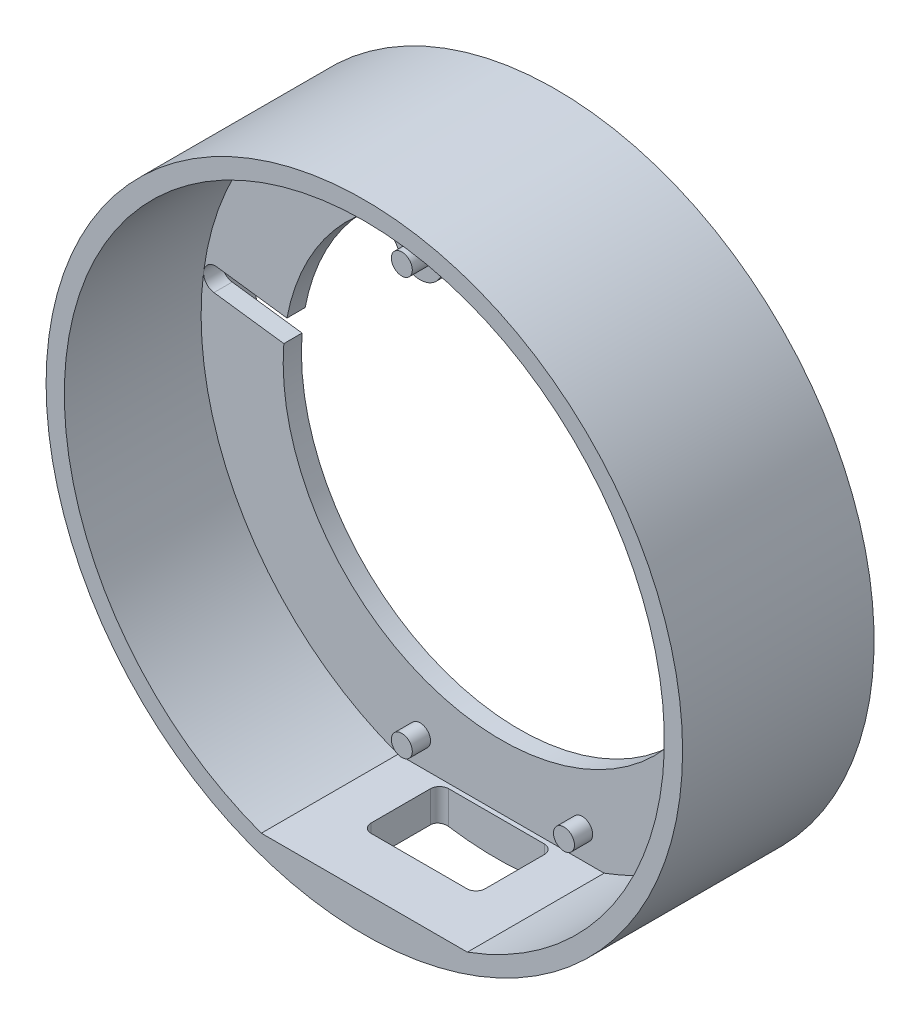
SolidWorks part; units mm, degrees
ref_plane "Plan de face" through (0, 0, 0) normal (0, 0, 1) x (1, 0, 0)
ref_plane "Plan de dessus" through (0, 0, 0) normal (0, 1, 0) x (1, 0, 0)
ref_plane "Plan de droite" through (0, 0, 0) normal (1, 0, 0) x (0, 0, -1)
sketch "Esquisse_carte_affichage" plane through (0, 0, 0) normal (0, 0, 1) x (1, 0, 0)
  circle A0 centre (19.25, 25.1) radius 0.5
  circle A1 centre (25.07, -19.23) radius 0.5
  circle A2 centre (29.18, 12.09) radius 0.5
  circle A3 centre (31.32, -4.14) radius 0.5
  circle A4 centre (-29.21, -12.07) radius 0.5
  circle A5 centre (-31.32, 4.14) radius 0.5
  circle A6 centre (-26.4935, -7.4094) radius 0.25
  circle A7 centre (-23.6728, -14.0139) radius 0.25
  circle A8 centre (-19.2392, -19.6637) radius 0.25
  circle A9 centre (-13.4943, -23.973) radius 0.25
  circle A10 centre (-6.8298, -26.6487) radius 0.25
  circle A11 centre (0.3, -27.5085) radius 0.25
  circle A12 centre (7.4094, -26.4935) radius 0.25
  circle A13 centre (14.0139, -23.6728) radius 0.25
  circle A14 centre (19.6637, -19.2392) radius 0.25
  circle A15 centre (23.973, -13.4943) radius 0.25
  circle A16 centre (26.6487, -6.8298) radius 0.25
  circle A17 centre (27.5085, 0.3) radius 0.25
  circle A18 centre (26.4935, 7.4094) radius 0.25
  circle A19 centre (23.6728, 14.0139) radius 0.25
  circle A20 centre (19.2392, 19.6637) radius 0.25
  circle A21 centre (13.4943, 23.973) radius 0.25
  circle A22 centre (6.8298, 26.6487) radius 0.25
  circle A23 centre (-0.3, 27.5085) radius 0.25
  circle A24 centre (-7.4094, 26.4935) radius 0.25
  circle A25 centre (-14.0139, 23.6728) radius 0.25
  circle A26 centre (-19.6637, 19.2392) radius 0.25
  circle A27 centre (-23.973, 13.4943) radius 0.25
  circle A28 centre (-26.6487, 6.8298) radius 0.25
  circle A29 centre (-27.5085, -0.3) radius 0.25
  circle A30 centre (-30.2, -7.1) radius 0.25
  circle A31 centre (-26.5986, -15.746) radius 0.25
  circle A32 centre (-28.1305, -7.8674) radius 0.25
  circle A33 centre (-21.6169, -22.0937) radius 0.25
  circle A34 centre (-25.1358, -14.8801) radius 0.25
  circle A35 centre (-15.162, -26.9359) radius 0.25
  circle A36 centre (-20.428, -20.8785) radius 0.25
  circle A37 centre (-7.6738, -29.9423) radius 0.25
  circle A38 centre (-14.3281, -25.4544) radius 0.25
  circle A39 centre (0.3371, -30.9082) radius 0.25
  circle A40 centre (-7.252, -28.2956) radius 0.25
  circle A41 centre (8.3254, -29.7678) radius 0.25
  circle A42 centre (0.3185, -29.2082) radius 0.25
  circle A43 centre (15.746, -26.5986) radius 0.25
  circle A44 centre (7.8674, -28.1305) radius 0.25
  circle A45 centre (22.0937, -21.6169) radius 0.25
  circle A46 centre (14.8801, -25.1358) radius 0.25
  circle A47 centre (26.9359, -15.162) radius 0.25
  circle A48 centre (20.8785, -20.428) radius 0.25
  circle A49 centre (29.9423, -7.6738) radius 0.25
  circle A50 centre (25.4544, -14.3281) radius 0.25
  circle A51 centre (30.9082, 0.3371) radius 0.25
  circle A52 centre (28.2956, -7.252) radius 0.25
  circle A53 centre (29.7678, 8.3254) radius 0.25
  circle A54 centre (29.2082, 0.3185) radius 0.25
  circle A55 centre (26.5986, 15.746) radius 0.25
  circle A56 centre (28.1305, 7.8674) radius 0.25
  circle A57 centre (21.6169, 22.0937) radius 0.25
  circle A58 centre (25.1358, 14.8801) radius 0.25
  circle A59 centre (15.162, 26.9359) radius 0.25
  circle A60 centre (20.428, 20.8785) radius 0.25
  circle A61 centre (7.6738, 29.9423) radius 0.25
  circle A62 centre (14.3281, 25.4544) radius 0.25
  circle A63 centre (-0.3371, 30.9082) radius 0.25
  circle A64 centre (7.252, 28.2956) radius 0.25
  circle A65 centre (-8.3254, 29.7678) radius 0.25
  circle A66 centre (-0.3185, 29.2082) radius 0.25
  circle A67 centre (-15.746, 26.5986) radius 0.25
  circle A68 centre (-7.8674, 28.1305) radius 0.25
  circle A69 centre (-22.0937, 21.6169) radius 0.25
  circle A70 centre (-14.8801, 25.1358) radius 0.25
  circle A71 centre (-26.9359, 15.162) radius 0.25
  circle A72 centre (-20.8785, 20.428) radius 0.25
  circle A73 centre (-29.9423, 7.6738) radius 0.25
  circle A74 centre (-25.4544, 14.3281) radius 0.25
  circle A75 centre (-30.9082, -0.3371) radius 0.25
  circle A76 centre (-28.2956, 7.252) radius 0.25
  circle A77 centre (0, 0) radius 26.162
  circle A78 centre (0, 0) radius 32.766
  dimension "D1" = 65.532
  dimension "D2" = 52.324
sketch "Esquisse_carte_mère" plane through (0, 0, 0) normal (0, 0, 1) x (1, 0, 0)
  line L0 (-11.3435, -28.5174) -> (-11.0897, -29.13)
  line L1 (-11.0897, -29.13) -> (-10.6861, -29.6561)
  line L2 (-10.6861, -29.6561) -> (-10.16, -30.0597)
  line L3 (-10.16, -30.0597) -> (-9.5474, -30.3135)
  line L4 (-9.5474, -30.3135) -> (-8.89, -30.4)
  line L5 (-8.89, -30.4) -> (-2.413, -30.4)
  line L6 (-2.413, -30.4) -> (-1.905, -29.892)
  line L7 (-1.905, -29.892) -> (1.905, -29.892)
  line L8 (1.905, -29.892) -> (2.413, -30.4)
  line L9 (2.413, -30.4) -> (8.89, -30.4)
  line L10 (8.89, -30.4) -> (9.5474, -30.3135)
  line L11 (9.5474, -30.3135) -> (10.16, -30.0597)
  line L12 (10.16, -30.0597) -> (10.6861, -29.6561)
  line L13 (10.6861, -29.6561) -> (11.0897, -29.13)
  line L14 (11.0897, -29.13) -> (11.3435, -28.5174)
  line L15 (11.3435, -28.5174) -> (11.43, -27.86)
  line L16 (11.43, -27.86) -> (11.43, 17.86)
  line L17 (11.43, 17.86) -> (11.3435, 18.5174)
  line L18 (11.3435, 18.5174) -> (11.0897, 19.13)
  line L19 (11.0897, 19.13) -> (10.6861, 19.6561)
  line L20 (10.6861, 19.6561) -> (10.16, 20.0597)
  line L21 (10.16, 20.0597) -> (9.5474, 20.3135)
  line L22 (9.5474, 20.3135) -> (8.89, 20.4)
  line L23 (8.89, 20.4) -> (-8.89, 20.4)
  line L24 (-8.89, 20.4) -> (-9.5474, 20.3135)
  line L25 (-9.5474, 20.3135) -> (-10.16, 20.0597)
  line L26 (-10.16, 20.0597) -> (-10.6861, 19.6561)
  line L27 (-10.6861, 19.6561) -> (-11.0897, 19.13)
  line L28 (-11.0897, 19.13) -> (-11.3435, 18.5174)
  line L29 (-11.3435, 18.5174) -> (-11.43, 17.86)
  line L30 (-11.43, 17.86) -> (-11.43, -27.86)
  line L31 (-11.43, -27.86) -> (-11.3435, -28.5174)
  line L32 (8.9522, -28.0199) -> (-18113.3609, 46572.2136) construction
  line L33 (-8.9266, -27.9541) -> (18113.3865, 46572.2795) construction
  circle A0 centre (-3.3, -25.05) radius 0.4
  circle A1 centre (3.3, -25.05) radius 0.4
  circle A2 centre (-3.6, -27.86) radius 0.45
  circle A3 centre (3.6, -27.86) radius 0.45
  circle A4 centre (10.16, 14.05) radius 0.5
  circle A5 centre (10.16, 11.51) radius 0.5
  circle A6 centre (10.16, 8.97) radius 0.5
  circle A7 centre (10.16, 6.43) radius 0.5
  circle A8 centre (10.16, 3.89) radius 0.5
  circle A9 centre (10.16, 1.35) radius 0.5
  circle A10 centre (10.16, -1.19) radius 0.5
  circle A11 centre (10.16, -3.73) radius 0.5
  circle A12 centre (10.16, -6.27) radius 0.5
  circle A13 centre (10.16, -8.81) radius 0.5
  circle A14 centre (10.16, -11.35) radius 0.5
  circle A15 centre (10.16, -13.89) radius 0.5
  circle A16 centre (-10.16, -24.05) radius 0.5
  circle A17 centre (-10.16, -21.51) radius 0.5
  circle A18 centre (-10.16, -18.97) radius 0.5
  circle A19 centre (-10.16, -16.43) radius 0.5
  circle A20 centre (-10.16, -13.89) radius 0.5
  circle A21 centre (-10.16, -11.35) radius 0.5
  circle A22 centre (-10.16, -8.81) radius 0.5
  circle A23 centre (-10.16, -6.27) radius 0.5
  circle A24 centre (-10.16, -3.73) radius 0.5
  circle A25 centre (-10.16, -1.19) radius 0.5
  circle A26 centre (-10.16, 1.35) radius 0.5
  circle A27 centre (-10.16, 3.89) radius 0.5
  circle A28 centre (-10.16, 6.43) radius 0.5
  circle A29 centre (-10.16, 8.97) radius 0.5
  circle A30 centre (-10.16, 11.51) radius 0.5
  circle A31 centre (-10.16, 14.05) radius 0.5
  circle A32 centre (-8.89, -27.86) radius 1.25
  circle A33 centre (8.89, -27.86) radius 1.25
  circle A34 centre (-8.89, 17.86) radius 1.25
  circle A35 centre (8.89, 17.86) radius 1.25
  circle A36 centre (-1.95, -25.955) radius 0.35
  circle A37 centre (1.95, -25.955) radius 0.35
  circle A38 centre (-2.2, 15.706) radius 0.45
  circle A39 centre (3.048, -15.795) radius 0.25
  circle A40 centre (1.016, -20.875) radius 0.25
  circle A41 centre (-6.223, -9.826) radius 0.25
  circle A42 centre (-6.096, -16.43) radius 0.25
  circle A43 centre (7.3914, -2.0028) radius 0.25
  circle A44 centre (7.366, -18.462) radius 0.25
  circle A45 centre (-1.905, 12.018) radius 0.25
  circle A46 centre (1.905, 9.224) radius 0.25
  circle A47 centre (-5.715, -21.129) radius 0.25
  circle A48 centre (-4.064, -1.571) radius 0.25
  circle A49 centre (-8.509, -22.78) radius 0.25
  circle A50 centre (0.2286, -14.5758) radius 0.25
  circle A51 centre (0.508, 7.446) radius 0.25
  circle A52 centre (0.635, 8.589) radius 0.25
  circle A53 centre (-7.112, 0.334) radius 0.25
  circle A54 centre (4.953, -15.795) radius 0.25
  circle A55 centre (0, 10.494) radius 0.25
  circle A56 centre (-4.191, -16.43) radius 0.25
  circle A57 centre (-0.889, -17.573) radius 0.25
  circle A58 centre (5.842, -10.715) radius 0.25
  circle A59 centre (2.159, -17.446) radius 0.25
  circle A60 centre (0, -27.987) radius 0.25
  circle A61 centre (-1.397, 4.271) radius 0.25
  circle A62 centre (-5.207, 1.985) radius 0.25
  circle A63 centre (-0.381, -6.651) radius 0.25
  circle A64 centre (6.858, 8.462) radius 0.25
  circle A65 centre (5.207, 3.128) radius 0.25
  circle A66 centre (2.667, 4.525) radius 0.25
  circle A67 centre (5.08, 11.764) radius 0.25
  circle A68 centre (0, 14.431) radius 0.25
  circle A69 centre (-1.778, 8.716) radius 0.25
  circle A70 centre (-2.921, 4.271) radius 0.25
  circle A71 centre (-5.588, 3.128) radius 0.25
  circle A72 centre (-1.905, -19.732) radius 0.25
  circle A73 centre (-5.842, -8.683) radius 0.25
  circle A74 centre (-3.048, -20.113) radius 0.25
  circle A75 centre (-6.604, -7.667) radius 0.25
  circle A76 centre (-5.207, -10.842) radius 0.25
  circle A77 centre (10.668, -26.082) radius 0.25
  circle A78 centre (5.969, -4.365) radius 0.25
  circle A79 centre (5.08, -9.191) radius 0.25
  circle A80 centre (-3.81, -3.349) radius 0.25
  circle A81 centre (-4.953, -9.699) radius 0.25
  circle A82 centre (3.048, 6.43) radius 0.25
  circle A83 centre (5.969, -3.222) radius 0.25
  circle A84 centre (6.858, -7.667) radius 0.25
  circle A85 centre (6.477, 6.303) radius 0.25
  circle A86 centre (-1.27, 10.367) radius 0.25
  circle A87 centre (-1.0922, -0.1994) radius 0.25
  circle A88 centre (0.508, -0.428) radius 0.25
  circle A89 centre (4.318, -17.065) radius 0.25
  circle A90 centre (1.524, 4.144) radius 0.25
  circle A91 centre (-2.921, -1.444) radius 0.25
  circle A92 centre (3.302, -10.08) radius 0.25
  circle A93 centre (-3.81, -10.08) radius 0.25
  circle A94 centre (-5.08, -6.778) radius 0.25
  point P222 (0, -5)
  dimension "D5" = 2.5
  dimension "D1" = 2.54
  dimension "D2" = 2.54
  dimension "D3" = 2.54
  dimension "D4" = 2.54
sketch "Esquisse_support" plane through (0, 0, 0) normal (0, 0, 1) x (1, 0, 0)
  line L0 (0, 0) -> (0, -50000) construction
  line L1 (0, 0) -> (-31.32, 4.14) construction
  line L2 (0, 0) -> (19.25, 25.1) construction
  line L3 (0, 0) -> (25.07, -19.23) construction
  line L4 (25.07, -19.23) -> (30456.2807, 39653.7005) construction
  line L5 (19.25, 25.1) -> (39694.4792, -30403.1136) construction
  line L6 (-31.32, 4.14) -> (6520.8813, 49572.9675) construction
  line L7 (-31.1487, 5.4363) -> (-23.4871, 4.4235)
  line L8 (-31.4913, 2.8437) -> (-23.8298, 1.831)
  line L9 (18.2437, 25.8718) -> (13.5179, 19.7098)
  line L10 (20.2563, 24.3282) -> (15.5305, 18.1663)
  line L11 (25.8637, -18.1952) -> (19.7291, -13.4897)
  line L12 (24.2763, -20.2648) -> (18.1417, -15.5592)
  line L13 (-8.89, 17.86) -> (46591.3436, 18140.1731) construction
  line L14 (8.89, 17.86) -> (-46591.3436, 18140.1731) construction
  line L15 (11.22, 16.9539) -> (13.5179, 19.7098)
  line L16 (72498.2044, -186428.9542) -> (-90602.6131, 232973.148) construction
  line L17 (-72498.1788, -186428.8884) -> (90602.6387, 232973.2138) construction
  circle A0 centre (0, 0) radius 32.9 construction
  circle A1 centre (0, 0) radius 34.9
  arc A2 (-32.6163, 4.3113) -> (-31.4913, 2.8437) centre (-31.32, 4.14) ccw
  arc A3 (-32.6163, 4.3113) -> (-31.1487, 5.4363) centre (-31.32, 4.14) cw
  arc A4 (20.0218, 26.1063) -> (18.2437, 25.8718) centre (19.25, 25.1) ccw
  arc A5 (20.0218, 26.1063) -> (20.2563, 24.3282) centre (19.25, 25.1) cw
  arc A6 (26.1048, -20.0237) -> (25.8637, -18.1952) centre (25.07, -19.23) ccw
  arc A7 (26.1048, -20.0237) -> (24.2763, -20.2648) centre (25.07, -19.23) cw
  arc A8 (-23.4871, 4.4235) -> (13.5179, 19.7098) centre (0, 0) cw construction
  arc A9 (-23.8298, 1.831) -> (18.1417, -15.5592) centre (0, 0) ccw
  arc A10 (19.7291, -13.4897) -> (15.5305, 18.1663) centre (0, 0) ccw
  arc A11 (-6.56, 18.7661) -> (-11.22, 16.9539) centre (-8.89, 17.86) cw
  arc A12 (6.56, 18.7661) -> (11.22, 16.9539) centre (8.89, 17.86) ccw
  arc A13 (-6.56, 18.7661) -> (-4.1838, 23.531) centre (-3.28, 20.1053) cw
  arc A14 (6.56, 18.7661) -> (4.1838, 23.531) centre (3.28, 20.1053) ccw
  arc A15 (-11.22, 16.9539) -> (-15.8818, 17.86) centre (-13.8724, 15.7529) ccw
  arc A16 (-23.4871, 4.4235) -> (-15.8818, 17.86) centre (0, 0) cw
  arc A17 (-4.1838, 23.531) -> (4.1838, 23.531) centre (0, 0) cw
  point P37 (-4.1838, 23.531)
  dimension "D1" = 65.8
  dimension "D2" = 69.8
  dimension "D12" = 2.5
  dimension "D13" = 2.5
  dimension "D3" = 90
  dimension "D4" = 90
  dimension "D5" = 90
  dimension "D7" = 90
  dimension "D8" = 90
  dimension "D9" = 90
  dimension "D10" = 90
  dimension "D11" = 90
extrude "Boss.-Extru.1" add sketch "Esquisse_support" along normal blind 2 contours A1 A13 A17 A14 A12 L15 L9 A4 A5 L10 A10 L11 A6 A7 L12 A9 L8 A2 A3 L7 A16 A15 A11 region at (-33.9129, 0, 0)
sketch "Esquisse6" plane through (0, 0, 2) normal (0, 0, 1) x (1, 0, 0)
  line L0 (0, 0) -> (0, -50000) construction
  circle A0 centre (-8.89, 17.86) radius 1.15
  circle A1 centre (-8.89, -27.86) radius 1.15
  circle A2 centre (8.89, -27.86) radius 1.15
  circle A3 centre (8.89, 17.86) radius 1.15
  dimension "D1" = 2.3
  dimension "D2" = 2.3
extrude "Boss.-Extru.2" add sketch "Esquisse6" along normal blind 2
sketch "Esquisse7" plane through (0, 0, 0) normal (0, 0, -1) x (-1, 0, 0)
  circle A0 centre (0, 0) radius 34.9
  circle A1 centre (0, 0) radius 32.9
extrude "Boss.-Extru.3" add sketch "Esquisse7" along normal blind 4
sketch "Esquisse8" plane through (0, 0, 2) normal (0, 0, 1) x (1, 0, 0)
  line L0 (0, 0) -> (0, -50000) construction
  line L1 (-11.296, -30.9) -> (11.296, -30.9)
  line L2 (-8.89, -30.4) -> (-2.413, -30.4) construction
  circle A0 centre (0, 0) radius 34.9
  circle A1 centre (0, 0) radius 32.9 construction
  arc A2 (-11.296, -30.9) -> (11.296, -30.9) centre (0, 0) cw
  point P9 (0, -30.9)
  circle M5 centre (0, 0) radius 34.9
  dimension "D2" = 0.5
extrude "Boss.-Extru.5" add sketch "Esquisse8" along normal blind 15 contours A2 L1 M5 region at (-33.9129, 0, 2)
sketch "Ouverture_USB" plane through (0, -30.9, 0) normal (0, 1, 0) x (1, 0, 0)
  line L0 (0, -16.2747) -> (0, 5.3613) construction
  line L2 (-5.25, -11) -> (5.25, -11)
  line L3 (-6.25, -10) -> (-6.25, -3.5)
  line L4 (-5.25, -2.5) -> (5.25, -2.5)
  line L5 (6.25, -10) -> (6.25, -3.5)
  arc A0 (6.25, -10) -> (5.25, -11) centre (5.25, -10) cw
  arc A1 (6.25, -3.5) -> (5.25, -2.5) centre (5.25, -3.5) ccw
  arc A2 (-5.25, -2.5) -> (-6.25, -3.5) centre (-5.25, -3.5) ccw
  arc A3 (-6.25, -10) -> (-5.25, -11) centre (-5.25, -10) ccw
  dimension "D4" = 1
  dimension "D1" = 8.5
  dimension "D2" = 12.5
  dimension "D3" = 2.5
extrude "Enlèv. mat.-Extru.1" cut sketch "Ouverture_USB" against normal blind 10
